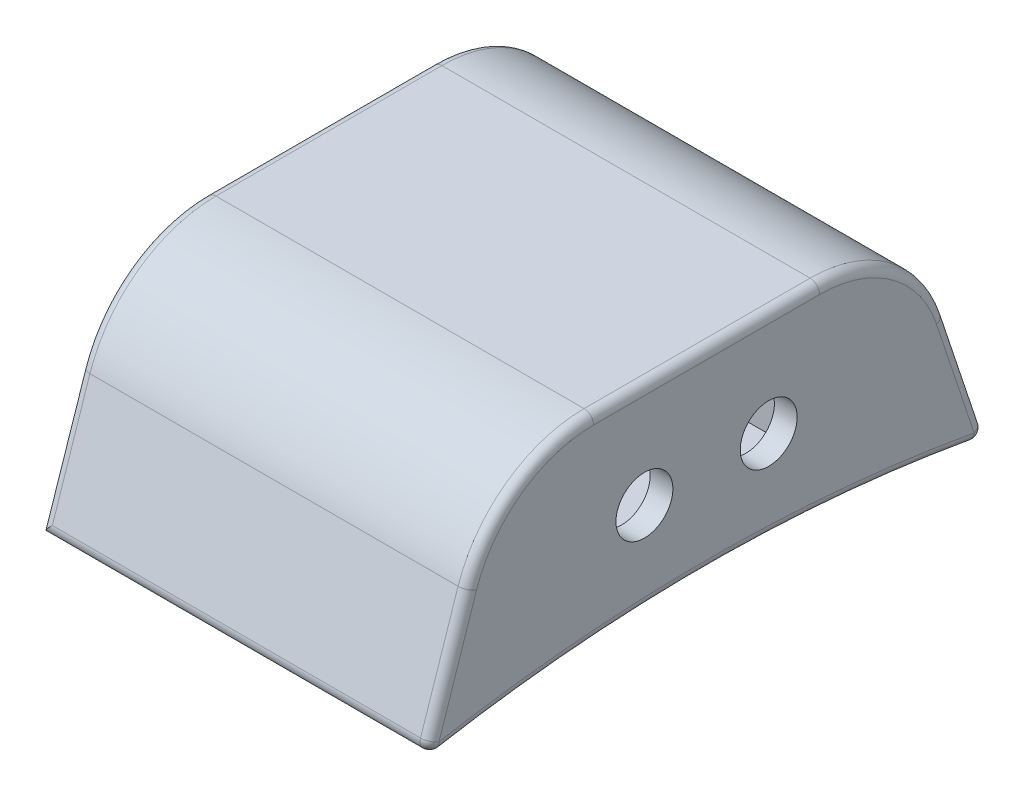
SolidWorks part; units mm, degrees
ref_plane "Front Plane" through (0, 0, 0) normal (0, 0, 1) x (1, 0, 0)
ref_plane "Top Plane" through (0, 0, 0) normal (0, 1, 0) x (1, 0, 0)
ref_plane "Right Plane" through (0, 0, 0) normal (1, 0, 0) x (0, 0, -1)
sketch "Sketch1" plane through (0, 0, 0) normal (1, 0, 0) x (0, 0, -1)
  line L0 (6.25, 5.8) -> (6.25, -0.8) construction
  line L7 (12.8, -0.8) -> (-0.3, -0.8)
  line L8 (12.8, 5.8) -> (12.8, -0.8)
  line L9 (-0.3, -0.8) -> (-0.3, 5.8)
  line L10 (-8.75, -4) -> (-4.75, 8)
  line L11 (21.25, -4) -> (-8.75, -4)
  line L12 (17.25, 8) -> (21.25, -4)
  line L13 (-4.75, 8) -> (17.25, 8)
  line L14 (-0.3, 5.8) -> (12.8, 5.8)
  point P3 (6.25, 8)
  point P4 (9.525, 2.5)
  point P9 (0, 0)
  point P14 (6.25, -4)
  point P16 (2.975, 2.5)
  point P17 (6.25, -4)
  point P18 (6.25, -0.3)
  point P19 (6.25, 2.5)
  point P20 (0, 0)
  point P21 (0, 0)
  dimension "D1" = 6.6
  dimension "D2" = 13.1
  dimension "D3" = 4
  dimension "D4" = 8.75
  dimension "D5" = 30
  dimension "D6" = 3.2
  dimension "D7" = 22
  dimension "D8" = 12
  dimension "D9" = 3.275
extrude "Boss-Extrude1" add sketch "Sketch1" along normal blind 9.2 and the other way blind 10
sketch "Sketch2" plane through (9.2, 0, 0) normal (1, 0, 0) x (0, 0, -1)
  line L0 (-4.75, 8) -> (-8.75, -4) construction
  line L1 (17.25, 8) -> (-4.75, 8) construction
  line L2 (21.25, -4) -> (17.25, 8) construction
  line L3 (-4.75, 8) -> (-8.75, -4)
  line L4 (17.25, 8) -> (-4.75, 8)
  line L5 (21.25, -4) -> (17.25, 8)
  line L7 (6.25, -0.8) -> (6.25, 5.8) construction
  line L8 (-0.3, -0.8) -> (12.8, -0.8) construction
  circle A2 centre (9.525, 2.5) radius 1.5
  circle A3 centre (2.975, 2.5) radius 1.5
  point P1 (0, 0)
  point P3 (0, 0)
  point P10 (6.25, 6.3)
  line M1 (-8.75, -4) -> (21.25, -4)
  line M2 (21.25, -4) -> (17.25, 8)
  line M3 (17.25, 8) -> (-4.75, 8)
  line M4 (-4.75, 8) -> (-8.75, -4)
  line M5 (12.8, 5.8) -> (12.8, -0.8)
  line M6 (12.8, -0.8) -> (-0.3, -0.8)
  line M7 (-0.3, -0.8) -> (-0.3, 5.8)
  line M8 (-0.3, 5.8) -> (12.8, 5.8)
  dimension "D1" = 3
extrude "Boss-Extrude2" add sketch "Sketch2" along normal blind 1.2 contours M4 M1 M2 M3 M8 M5 M6 M7 | A3 A2 M5 M8 M7 M6 | L7 A2 M6 M5 M8 region at (9.2, 7.6769, -6.25) region at (9.2, -0.707, -2.975) region at (9.2, 2.5, -6.343)
sketch "Sketch3" plane through (10.4, 0, 0) normal (1, 0, 0) x (0, 0, -1)
  line L0 (-4.75, 8) -> (-8.75, -4) construction
  line L1 (21.25, -4) -> (17.25, 8) construction
  line L2 (21.0919, -3.5257) -> (21.25, -4)
  line L3 (21.25, -4) -> (-8.75, -4)
  line L4 (-8.75, -4) -> (-8.5919, -3.5257)
  arc A0 (-8.5919, -3.5257) -> (21.0919, -3.5257) centre (6.25, -82.1368) cw
  dimension "D1" = 80
  dimension "D2" = 0.5
extrude "Cut-Extrude1" cut sketch "Sketch3" against normal up to surface (20.4 mm away) up to face at (-10, 2.5, -6.25)
fillet "Fillet1" radius 7 2 edges at (0.2, 8, -17.25) (0.2, 8, 4.75)
ref_plane "Plane1" through (0, -3.5257, 0) normal (0, 1, 0) x (1, 0, 0)
sketch "Sketch4" plane through (0, -3.5257, 0) normal (0, 1, 0) x (1, 0, 0)
  line L2 (10.4, -8.5919) -> (10.4, 21.0919) construction
  line L3 (3.4, -1.3) -> (3.4, 13.8) construction
  circle A0 centre (3.4, 13.8) radius 1.5
  circle A1 centre (3.4, -1.3) radius 1.5
  point P4 (0, 0)
  point P5 (10.4, 6.25)
  point P6 (3.4, 6.25)
  dimension "D1" = 3
  dimension "D2" = 7
  dimension "D3" = 15.1
extrude "Boss-Extrude3" add sketch "Sketch4" along normal up to surface (2.7257 mm away) and the other way blind 1 up to face at (-0.4, -0.8, -6.25)
sketch "Sketch5" plane through (0, -3.5257, 0) normal (0, 1, 0) x (1, 0, 0)
  line L0 (-7.1, -3.75) -> (-7.1, 16.25) construction
  line L1 (10.4, -8.5919) -> (10.4, 21.0919) construction
  circle A0 centre (-7.1, 16.25) radius 1.4
  circle A1 centre (-7.1, -3.75) radius 1.4
  point P6 (10.4, 6.25)
  point P7 (-7.1, 6.25)
  dimension "D1" = 2.8
  dimension "D2" = 20
  dimension "D3" = 10.5
extrude "Cut-Extrude2" cut sketch "Sketch5" along normal blind 7
chamfer "Chamfer1" distance 0.25 angle 80 2 edges at (3.4, -4.5257, -12.3) (3.4, -4.5257, 2.8) first distance on face at (3.4, -4.5257, -12.3) first distance on face at (3.4, -4.5257, 2.8)
sketch "Sketch6" plane through (0, -3.5257, 0) normal (0, 1, 0) x (1, 0, 0)
  circle A0 centre (3.4, 13.8) radius 1.5 construction
  circle A1 centre (3.4, -1.3) radius 1.5 construction
  circle A2 centre (-7.1, -3.75) radius 1.4 construction
  circle A3 centre (-7.1, 16.25) radius 1.4 construction
  circle A4 centre (3.4, 13.8) radius 1.5
  circle A5 centre (3.4, -1.3) radius 1.5
  circle A6 centre (-7.1, -3.75) radius 1.4
  circle A7 centre (-7.1, 16.25) radius 1.4
fillet "Fillet2" radius 0.5 13 edges at (-10, -0.156, -19.9687) (-10, 6.6787, -16.2977) (-10, 8, -6.25) (-10, 6.6787, 3.7977) (10.4, -0.156, -19.9687) (10.4, 6.6787, -16.2977) (10.4, -0.156, 7.4687) (10.4, 6.6787, 3.7977) (10.4, -2.1368, -6.25) (0.2, -3.5257, -21.0919) (-10, -0.156, 7.4687) (10.4, 8, -6.25) (0.2, -3.5257, 8.5919)
